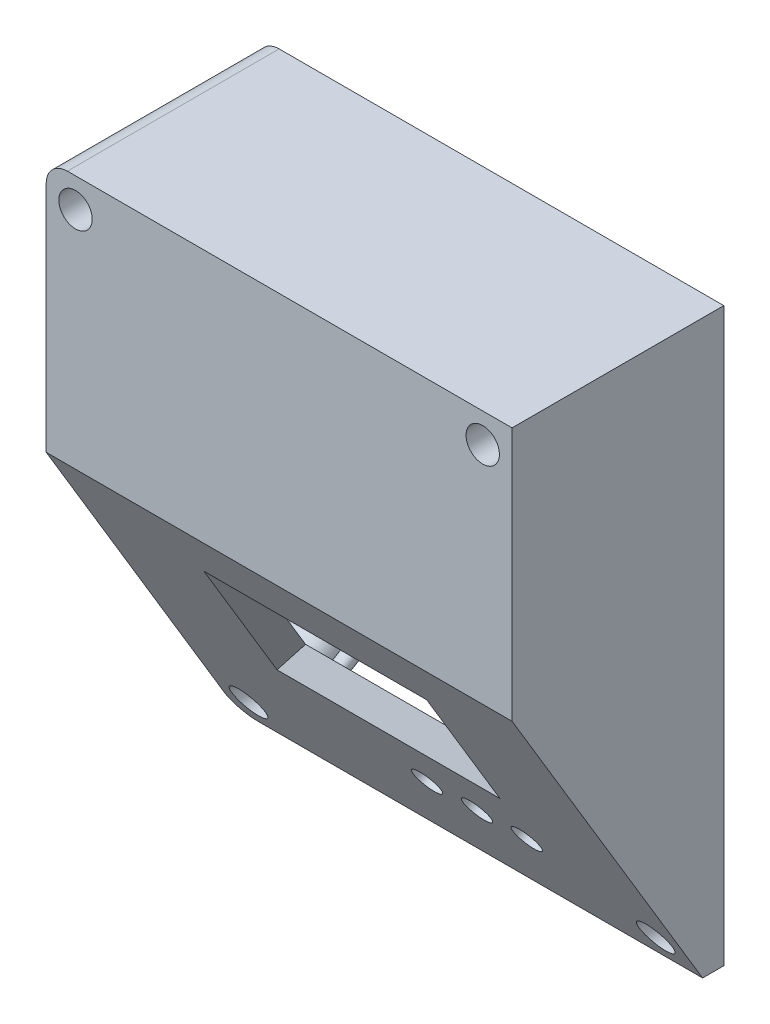
SolidWorks part; units mm, degrees
ref_plane "Front Plane" through (0, 0, 0) normal (0, 0, 1) x (1, 0, 0)
ref_plane "Top Plane" through (0, 0, 0) normal (0, 1, 0) x (1, 0, 0)
ref_plane "Right Plane" through (0, 0, 0) normal (1, 0, 0) x (0, 0, -1)
sketch "Sketch1" plane through (0, 0, 0) normal (0, 0, 1) x (1, 0, 0)
  line L0 (-92.5, 50) -> (-92.5, -50) construction
  line L1 (-4.5, 54) -> (-88.5, 54)
  line L2 (-4.5, 54) -> (-4.5, -54)
  line L3 (-4.5, -54) -> (-88.5, -54)
  line L4 (-92.5, 50) -> (-92.5, -50)
  line L5 (-88.5, -54) -> (-4.5, -54) construction
  arc A0 (-88.5, 54) -> (-92.5, 50) centre (-88.5, 50) ccw
  arc A1 (-88.5, -54) -> (-92.5, -50) centre (-88.5, -50) cw
  point P13 (-92.5, -54)
  dimension "D1" = 4
extrude "Boss-Extrude1" add sketch "Sketch1" along normal blind 40
sketch "Sketch2" plane through (-92.5, 0, 0) normal (-1, 0, 0) x (0, 0, 1)
  line L0 (40, -54) -> (40, 6)
  line L1 (40, 50) -> (40, -50) construction
  line L2 (40, 6) -> (4, -54)
  line L3 (40, -54) -> (0, -54) construction
  line L4 (4, -54) -> (40, -54)
  line L10 (0, -50) -> (0, -54) construction
  point P18 (0, 0)
  line M9 (0, -50) -> (40, -50)
  line M10 (40, -50) -> (40, 50)
  dimension "D1" = 60
  dimension "D2" = 4
extrude "Cut-Extrude1" cut sketch "Sketch2" against normal up to surface (88 mm away) contours L2 M10 M9 | L2 L4 L0 M9 region at (-92.5, -52.023, 22.5931) region at (-92.5, -31.3333, 28.8) up to face at (-4.5, 0, 20)
shell "Shell1" thickness 4 removed face at (-62.1095, 0, 0)
sketch "Sketch3" plane through (0, 0, 0) normal (0, 0, 1) x (1, 0, 0)
  circle A0 centre (-86.962, 48.462) radius 4.175
  circle A1 centre (-10.038, 48.462) radius 4.175
  circle A2 centre (-86.962, -48.462) radius 4.175
  circle A3 centre (-10.038, -48.462) radius 4.175
  arc A4 (-88.5, 44.5806) -> (-83.0806, 50) centre (-86.962, 48.462) ccw construction
  arc A5 (-13.9194, 50) -> (-8.5, 44.5806) centre (-10.038, 48.462) ccw construction
  arc A6 (-83.0806, -50) -> (-88.5, -44.5806) centre (-86.962, -48.462) ccw construction
  arc A7 (-8.5, -44.5806) -> (-13.9194, -50) centre (-10.038, -48.462) ccw construction
extrude "Boss-Extrude2" add sketch "Sketch3" along normal up to surface (7.3228 mm away) contours A2 | A3 up to face at (-56.6657, -29.3657, 18.7806)
extrude "Boss-Extrude3" add sketch "Sketch3<3>" along normal up to surface (40 mm away) contours A0 | A1 up to face at (-56.6657, 34.1657, 40)
sketch "Sketch3<3>" plane through (0, 0, 0) normal (0, 0, 1) x (1, 0, 0) same geometry as "Sketch3"
sketch "Sketch4" plane through (0, 0, 40) normal (0, 0, 1) x (1, 0, 0)
  circle A0 centre (-86.962, 48.462) radius 3.15
  arc A1 (-88.5, 44.5806) -> (-83.0806, 50) centre (-86.962, 48.462) ccw construction
  circle A2 centre (-10.038, 48.462) radius 3.15
  circle A3 centre (-10.038, -48.462) radius 3.15
  circle A4 centre (-86.962, -48.462) radius 3.15
  arc A5 (-13.9194, 50) -> (-8.5, 44.5806) centre (-10.038, 48.462) ccw construction
  arc A6 (-83.0806, -50) -> (-88.5, -44.5806) centre (-86.962, -48.462) ccw construction
  arc A7 (-8.5, -44.5806) -> (-13.9194, -50) centre (-10.038, -48.462) ccw construction
  circle A8 centre (-86.962, 48.462) radius 1.575
  circle A9 centre (-10.038, 48.462) radius 1.575
  circle A10 centre (-10.038, -48.462) radius 1.575
  circle A11 centre (-86.962, -48.462) radius 1.575
  point P24 (0, 0)
  dimension "D1" = 6.3
  dimension "D2" = 3.15
extrude "Cut-Extrude2" cut sketch "Sketch4" against normal up to surface (40 mm away) contours A8 | A9 | A10 | A11 up to face at (-48.5, 0, 0)
extrude "Cut-Extrude3" cut sketch "Sketch4<3>" against normal offset from surface (38.5 mm away) 1.5 up to face at (-88.537, -48.462, 0)
sketch "Sketch4<3>" plane through (0, 0, 40) normal (0, 0, 1) x (1, 0, 0) same geometry as "Sketch4"
sketch "Sketch5" plane through (0, -14.0008, 23.3347) normal (0, 0.5145, -0.8575) x (-1, 0, 0)
  circle A0 centre (79, -30.6712) radius 4.675
  circle A1 centre (18, -30.6712) radius 4.675
  circle A2 centre (79, 14.3288) radius 4.675
  circle A3 centre (18, 14.3288) radius 4.675
  circle A4 centre (79, 14.3288) radius 2.175
  circle A5 centre (18, 14.3288) radius 2.175
  circle A6 centre (18, -30.6712) radius 2.175
  circle A7 centre (79, -30.6712) radius 2.175
  circle A8 centre (79, -30.6712) radius 1.6 construction
  circle A9 centre (18, -30.6712) radius 1.6 construction
  circle A11 centre (79, 14.3288) radius 1.6 construction
  circle A12 centre (18, 14.3288) radius 1.6 construction
  dimension "D1" = 4.35
  dimension "D2" = 2.5
extrude "Boss-Extrude4" add sketch "Sketch5" along normal blind 7.5
sketch "Sketch6" plane through (0, -14.0008, 23.3347) normal (0, 0.5145, -0.8575) x (-1, 0, 0)
  line L1 (65.55, 8.4551) -> (31.45, 8.4551)
  line L2 (65.55, 8.4551) -> (65.55, -10.4449)
  line L3 (65.55, -10.4449) -> (31.45, -10.4449)
  line L4 (31.45, 8.4551) -> (31.45, -10.4449)
  line L13 (31.25, -10.6449) -> (31.25, 8.6551) construction
  line L14 (65.75, -10.6449) -> (31.25, -10.6449) construction
  point P6 (31.25, -8.2468)
  point P10 (65.75, -10.6449)
  point P12 (65.75, 8.6551)
  dimension "D1" = 0.2
  dimension "D2" = 0.2
  dimension "D3" = 0.2
  dimension "D4" = 0.2
extrude "Cut-Extrude4" cut sketch "Sketch6" against normal up to surface (4 mm away) up to face at (-86.962, -45.312, 9.2128)
chamfer "Chamfer1" distance 4 angle 45 4 edges at (-48.5, -25.0152, 21.3909) (-31.45, -16.9119, 26.2528) (-48.5, -8.8086, 31.1148) (-65.55, -16.9119, 26.2528)
ref_plane "Plane1" through (-83.0806, -50, 0) normal (1, 0, 0) x (0, 0, -1)
sketch "Sketch8" plane through (0, -16.0588, 26.7647) normal (0, -0.5145, 0.8575) x (1, 0, 0)
  circle A0 centre (-47.45, -26.5212) radius 2.65
  circle A1 centre (-37.95, -26.4212) radius 2.65
  circle A2 centre (-28.55, -26.4212) radius 2.65
  circle A3 centre (-47.45, -26.5212) radius 1.65 construction
  dimension "D1" = 1
extrude "Cut-Extrude5" cut sketch "Sketch8" against normal up to surface (4 mm away) up to face at (-48.5, -14.8539, 22.8229)
sketch "Sketch9" plane through (0, -14.0008, 23.3347) normal (0, 0.5145, -0.8575) x (-1, 0, 0)
  circle A0 centre (63, -16.3449) radius 1.4
  circle A1 centre (34, -16.3449) radius 1.4
  circle A2 centre (34, 10.6551) radius 1.4
  circle A3 centre (63, 10.6551) radius 1.4
  arc A4 (61.4, -16.3449) -> (64.6, -16.3449) centre (63, -16.3449) ccw construction
  dimension "D1" = 0.2
extrude "Boss-Extrude7" add sketch "Sketch9" along normal offset from surface (7.399 mm away) 4.5 offset beyond the face yes
